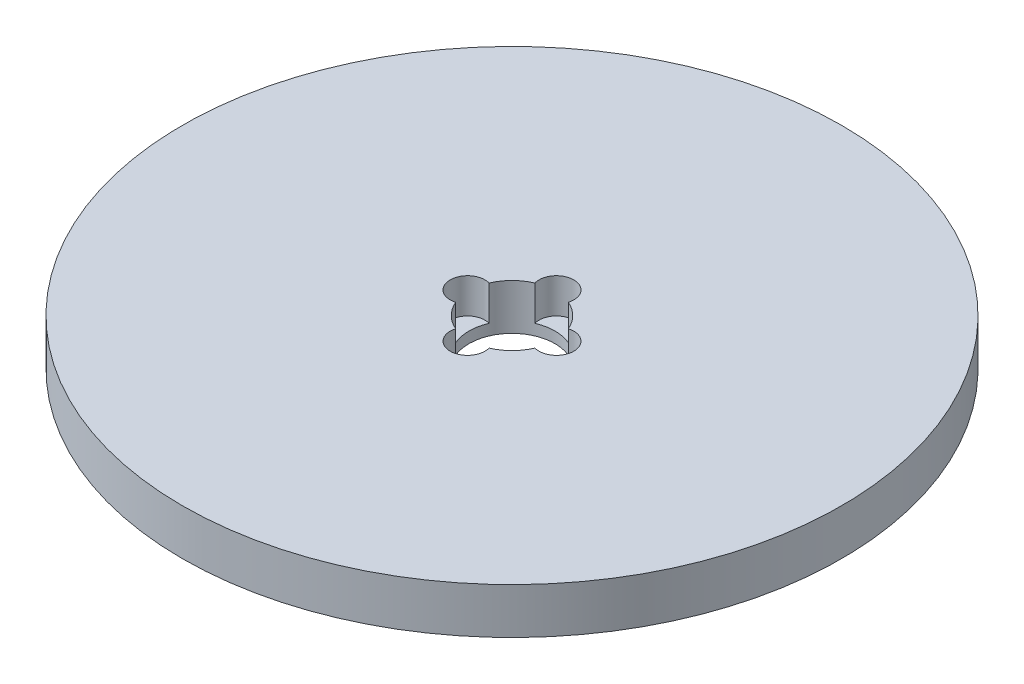
SolidWorks part; units mm, degrees
ref_plane "Front Plane" through (0, 0, 0) normal (0, 0, 1) x (1, 0, 0)
ref_plane "Top Plane" through (0, 0, 0) normal (0, 1, 0) x (1, 0, 0)
ref_plane "Right Plane" through (0, 0, 0) normal (1, 0, 0) x (0, 0, -1)
sketch "Sketch1" plane through (0, 0, 0) normal (0, 1, 0) x (1, 0, 0)
  circle A0 centre (0, 0) radius 57.5
  dimension "FLANGE_OD" = 115
extrude "Boss-Extrude1" add sketch "Sketch1" along normal blind 8
sketch "Sketch2" plane through (0, 0, 0) normal (0, 1, 0) x (1, 0, 0)
  circle A0 centre (0, 0) radius 7.5
  dimension "BORE_D" = 15
extrude "Cut-Extrude1" cut sketch "Sketch2" along normal through all
sketch "Sketch3" plane through (0, 8, 0) normal (0, 1, 0) x (1, 0, 0)
  circle A0 centre (0, 0) radius 7.7511 construction
  circle A1 centre (-7.7511, 0) radius 3.0334
  dimension "BOLT_D" = 6.0668
  dimension "BOLT_PCD" = 15.5022
extrude "Cut-Extrude2" cut sketch "Sketch3" against normal blind 6.0871
pattern_circular "CirPattern1" count 4 over 360 about axis through (0, 0, 0) along (0, 1, 0) of "Cut-Extrude2"
